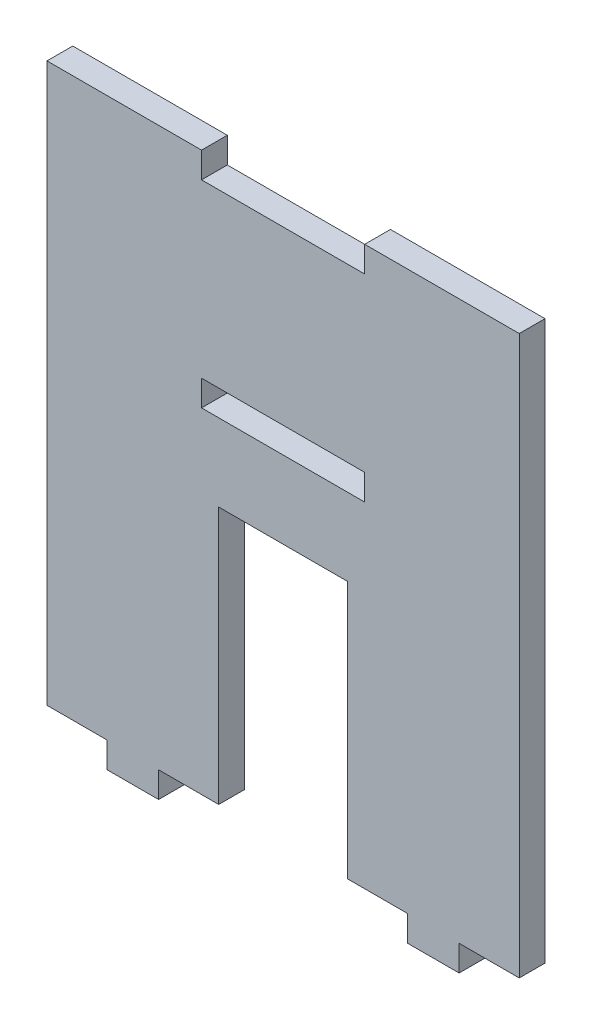
SolidWorks part; units mm, degrees
ref_plane "Front Plane" through (0, 0, 0) normal (0, 0, 1) x (1, 0, 0)
ref_plane "Top Plane" through (0, 0, 0) normal (0, 1, 0) x (1, 0, 0)
ref_plane "Right Plane" through (0, 0, 0) normal (1, 0, 0) x (0, 0, -1)
sketch "Sketch1" plane through (0, 0, 0) normal (0, 0, 1) x (1, 0, 0)
  line L0 (0, 0) -> (0, 65)
  line L1 (0, 65) -> (18, 65)
  line L2 (18, 65) -> (18, 62)
  line L3 (18, 62) -> (37, 62)
  line L4 (37, 62) -> (37, 65)
  line L5 (37, 65) -> (55, 65)
  line L6 (55, 65) -> (55, 0)
  line L7 (0, 0) -> (7, 0)
  line L8 (27.5, 62) -> (27.5, 42) construction
  line L9 (42, 0) -> (35, 0)
  line L10 (20, 30) -> (20, 0)
  line L11 (7, 0) -> (7, -3)
  line L12 (7, -3) -> (13, -3)
  line L13 (13, -3) -> (13, 0)
  line L14 (13, 0) -> (20, 0)
  line L15 (42, -3) -> (42, 0)
  line L16 (48, -3) -> (42, -3)
  line L17 (48, 0) -> (48, -3)
  line L18 (35, 30) -> (35, 0)
  line L19 (55, 0) -> (48, 0)
  line L20 (20, 30) -> (35, 30)
  line L21 (37, 42) -> (37, 39)
  line L22 (37, 42) -> (18, 42)
  line L23 (27.5, 42) -> (27.5, 39)
  line L24 (37, 39) -> (18, 39)
  line L25 (18, 42) -> (18, 39)
  dimension "D1" = 65
  dimension "D2" = 18
  dimension "D3" = 19
  dimension "D4" = 18
  dimension "D5" = 30
  dimension "D6" = 3
  dimension "D7" = 3
  dimension "D8" = 7
  dimension "D9" = 6
  dimension "D10" = 7
  dimension "D11" = 3
  dimension "D12" = 65
  dimension "D13" = 3
  dimension "D14" = 20
  dimension "D15" = 9.5
  dimension "D16" = 3
extrude "Boss-Extrude1" add sketch "Sketch1" along normal blind 3 contours L10 L20 L18 L9 L15 L16 L17 L19 L6 L5 L4 L3 L22 L21 L24 L25 L2 L1 L0 L7 L11 L12 L13 L14 region at (27.5, 33.9532, 0)
